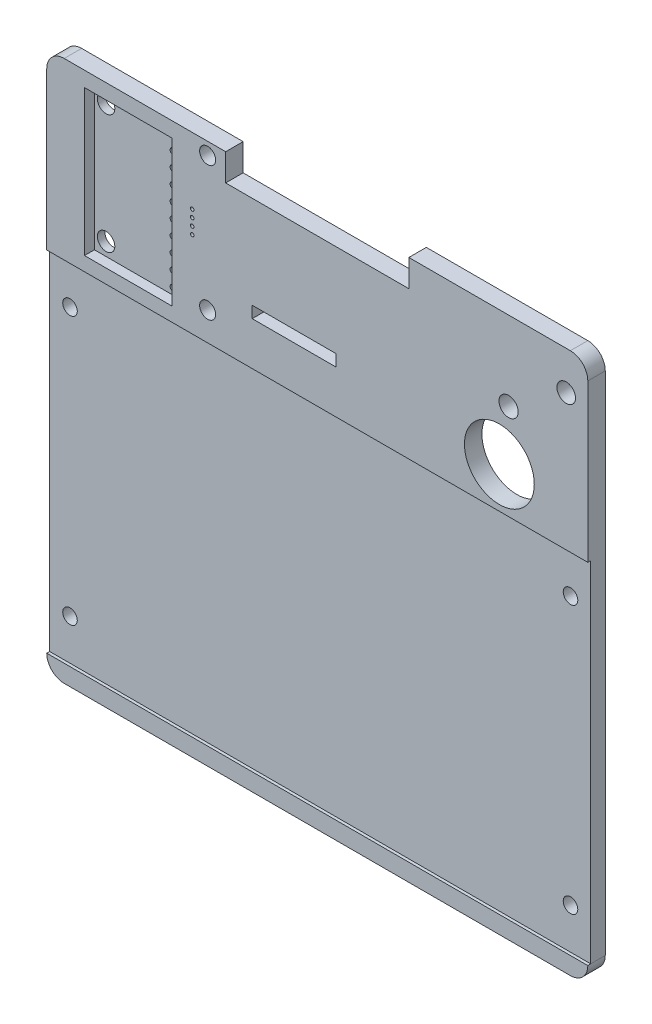
SolidWorks part; units mm, degrees
note: The reader was unsure of these and kept them because the rebuilt part matched: shared geometry of "Sketch2<5>", "Sketch2<6>", "Sketch2<7>", "Sketch7<3>".
ref_plane "Front Plane" through (0, 0, 0) normal (0, 0, 1) x (1, 0, 0)
ref_plane "Top Plane" through (0, 0, 0) normal (0, 1, 0) x (1, 0, 0)
ref_plane "Right Plane" through (0, 0, 0) normal (1, 0, 0) x (0, 0, -1)
sketch "Sketch1" plane through (0, 0, 0) normal (0, 0, 1) x (1, 0, 0)
  line L1 (-46.4872, 46.5) -> (46.4872, 46.5)
  line L2 (-46.4872, 46.5) -> (-46.4872, -46.5)
  line L3 (-46.4872, -46.5) -> (46.4872, -46.5)
  line L4 (46.4872, 46.5) -> (46.4872, -46.5)
  line L5 (-46.4872, 46.5) -> (46.4872, -46.5) construction
  line L6 (-46.4872, -46.5) -> (46.4872, 46.5) construction
  point P0 (0, 0)
  dimension "D1" = 93
  dimension "D2" = 92.9743
extrude "Boss-Extrude1" add sketch "Sketch1" along normal blind 3
fillet "Fillet1" radius 3 4 edges at (-46.4872, -46.5, 1.5) (46.4872, -46.5, 1.5) (46.4872, 46.5, 1.5) (-46.4872, 46.5, 1.5)
sketch "Sketch2" plane through (0, 0, 3) normal (0, 0, 1) x (1, 0, 0)
  line L7 (-46.4872, -43.5) -> (46.4872, -43.5)
  line L69 (43.4872, 46.5) -> (-43.4872, 46.5) construction
  line L76 (46.4872, -43.5) -> (46.5128, 16.5)
  line L82 (-46.4872, 16.5) -> (46.5128, 16.5)
  line L83 (-46.4872, 43.5) -> (-46.4872, -43.5) construction
  line L87 (-11.18, 23.93) -> (-11.18, 25.93)
  line L88 (-11.18, 25.93) -> (3.22, 25.93)
  line L89 (3.22, 25.93) -> (3.22, 23.93)
  line L90 (3.22, 23.93) -> (-11.18, 23.93)
  line L93 (-15.24, 46.5) -> (15.24, 46.5)
  line L96 (-15.24, 41.85) -> (15.74, 41.85)
  line L98 (-15.74, 46.5) -> (-15.74, 41.85)
  line L99 (15.74, 46.5) -> (15.74, 41.85)
  line L100 (15.24, 46.5) -> (15.74, 46.5)
  line L101 (-15.24, 41.85) -> (-15.74, 41.85)
  line L102 (-15.24, 46.5) -> (-15.74, 46.5)
  line L103 (0.0128, 18.9571) -> (0.0128, -60.266)
  line L104 (-46.4872, 16.5) -> (-46.4872, -43.5)
  line L105 (-46.4872, -13.5) -> (-41.3883, -13.5)
  circle A7 centre (-18.84, 21.39) radius 1.375
  circle A11 centre (-21.49, 35.08) radius 0.3
  circle A12 centre (-18.84, 44.39) radius 1.375
  circle A13 centre (-18.84, 21.39) radius 1.375
  circle A14 centre (-18.84, 44.39) radius 1.375
  circle A15 centre (-21.49, 35.08) radius 0.3
  circle A19 centre (-21.49, 33.81) radius 0.3
  circle A20 centre (-21.49, 32.54) radius 0.3
  circle A21 centre (-21.49, 31.27) radius 0.3
  circle A22 centre (-42.9887, 9.5) radius 1.25
  circle A23 centre (43.0143, 9.5) radius 1.25
  circle A24 centre (43.0143, -36.5) radius 1.25
  circle A25 centre (-42.9887, -36.5) radius 1.25
  point P6 (-42.9887, 9.5)
  point P12 (0, 46.5)
  point P17 (0, 46.5)
  point P26 (-46.4872, -13.5)
  point P42 (0, 0)
  point P73 (-18.84, 44.39)
  dimension "D53" = 2.75
  dimension "D12" = 23
  dimension "D11" = 3.1
  dimension "D2" = 6.77
  dimension "D4" = 5.75
  dimension "D5" = 93
  dimension "D6" = 9.43
  dimension "D7" = 3.6
  dimension "D8" = 2.11
  dimension "D9" = 4.65
  dimension "D10" = 0
  dimension "D13" = 46.5
  dimension "D14" = 46
  dimension "D38" = 14.4
  dimension "D39" = 2
  dimension "D50" = 23
sketch "Sketch4" plane through (0, 0, 3) normal (0, 0, 1) x (1, 0, 0)
  line L2 (46.4872, -43.5) -> (46.4872, 43.5) construction
  line L3 (43.4872, 46.5) -> (-43.4872, 46.5) construction
  circle A8 centre (42.7772, 39.9) radius 1.6
  circle A9 centre (32.8772, 32.89) radius 1.65
  point P0 (0, 0)
  point P1 (0, 0)
  point P2 (0, 0)
  point P3 (0, 0)
  point P22 (0, 0)
  point P30 (42.7772, 39.9)
  point P31 (32.8772, 32.89)
  point P32 (37.9872, 24.5)
  point P33 (40.5872, 9.1)
  point P34 (42.7772, 39.9)
  dimension "D17" = 6.6
  dimension "D18" = 3.71
  dimension "D19" = 13.61
  dimension "D20" = 13.61
  dimension "D21" = 8.5
  dimension "D22" = 22
  dimension "D23" = 5.9
  dimension "D24" = 37.4
extrude "Cut-Extrude3" cut sketch "Sketch4" against normal blind 3
extrude "Cut-Extrude5" cut sketch "Sketch2" against normal blind 10
extrude "Cut-Extrude6" cut sketch "Sketch2<5>" against normal blind 10 contours A19 | A20 | A21
sketch "Sketch2<5>" plane through (0, 0, 3) normal (0, 0, 1) x (1, 0, 0) same geometry as "Sketch2"
extrude "Cut-Extrude7" cut sketch "Sketch2<6>" against normal through all contours A22 | A25 | A23 | A24
sketch "Sketch2<6>" plane through (0, 0, 3) normal (0, 0, 1) x (1, 0, 0) same geometry as "Sketch2"
extrude "Cut-Extrude8" cut sketch "Sketch2<7>" against normal blind 0.5
sketch "Sketch2<7>" plane through (0, 0, 3) normal (0, 0, 1) x (1, 0, 0) same geometry as "Sketch2"
sketch "Sketch6" plane through (0, 0, 3) normal (0, 0, 1) x (1, 0, 0)
  line L0 (43.4872, 46.5) -> (15.74, 46.5) construction
  line L1 (46.4872, 16.5) -> (46.4872, 43.5) construction
  circle A0 centre (31.2872, 23.5) radius 6
  point P0 (31.2872, 23.5)
  dimension "D2" = 15.2
  dimension "D1" = 23
extrude "Cut-Extrude9" cut sketch "Sketch6" against normal through all
sketch "Sketch7" plane through (0, 0, 3) normal (0, 0, 1) x (1, 0, 0)
  line L1 (-40.0005, 43.9124) -> (-25.0005, 43.9124)
  line L2 (-40.0005, 43.9124) -> (-40.0005, 18.9124)
  line L3 (-40.0005, 18.9124) -> (-25.0005, 18.9124)
  line L4 (-25.0005, 43.9124) -> (-25.0005, 18.9124)
  circle A0 centre (-38.0005, 21.1624) radius 1.5
  circle A1 centre (-38.0005, 41.6624) radius 1.5
  circle A2 centre (-26.5005, 42.8424) radius 0.5
  circle A3 centre (-26.5005, 40.3024) radius 0.5
  circle A4 centre (-26.5005, 37.7624) radius 0.5
  circle A5 centre (-26.5005, 35.2224) radius 0.5
  circle A6 centre (-26.5005, 32.6824) radius 0.5
  circle A7 centre (-26.5005, 30.1424) radius 0.5
  circle A8 centre (-26.5005, 27.6024) radius 0.5
  circle A9 centre (-26.5005, 25.0624) radius 0.5
  circle A10 centre (-26.5005, 22.5224) radius 0.5
  circle A11 centre (-26.5005, 19.9824) radius 0.5
  point P10 (0, 0)
  point P11 (0, 0)
  dimension "D3" = 2.25
  dimension "D5" = 1.5
  dimension "D1" = 25
  dimension "D2" = 15
  dimension "D4" = 2
  dimension "D6" = 1.07
extrude "Cut-Extrude10" cut sketch "Sketch7" against normal blind 5 contours A2 | A3 | A4 | A5 | A6 | A7 | A8 | A10 | A11 | A9 | A1 | A0
extrude "Cut-Extrude11" cut sketch "Sketch7<3>" against normal blind 1.71
sketch "Sketch7<3>" plane through (0, 0, 3) normal (0, 0, 1) x (1, 0, 0) same geometry as "Sketch7"
